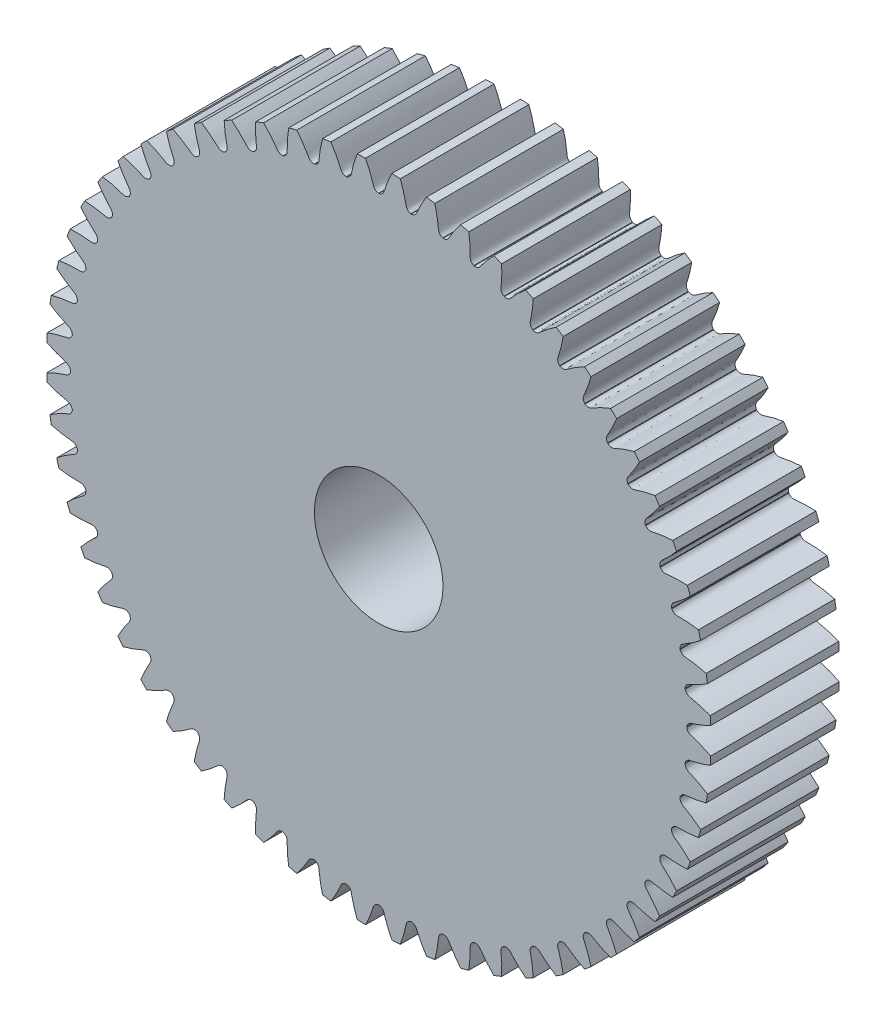
SolidWorks part; units mm, degrees
ref_plane "前视基准面" through (0, 0, 0) normal (0, 0, 1) x (1, 0, 0)
ref_plane "上视基准面" through (0, 0, 0) normal (0, 1, 0) x (1, 0, 0)
ref_plane "右视基准面" through (0, 0, 0) normal (1, 0, 0) x (0, 0, -1)
other "Configuration Table"
sketch "草图1" plane through (0, 0, 0) normal (0, 0, 1) x (1, 0, 0)
  circle A0 centre (0, 0) radius 15.5
extrude "凸台-拉伸1" add sketch "草图1" along normal blind 6
ref_axis "基准轴1" through (0, 0, -0.3) along (0, 0, 1)
sketch "草图2" plane through (0, 0, 0) normal (0, 0, 1) x (1, 0, 0)
  line L0 (0, 0) -> (0, 15.5) construction
  circle A0 centre (0, 0) radius 15.5 construction
  arc A1 (0.01, 14.375) -> (-0.01, 14.375) centre (0, 0) ccw
  arc A2 (2.1043, 17.5326) -> (-2.1043, 17.5326) centre (0, 0) ccw
  spline S0 degree 3 poles (0.01, 14.375) (0.2152, 14.4122) (0.2483, 14.5839) (0.3119, 14.7751) (0.342, 14.8616) (0.3759, 14.9526) (0.4137, 15.0482) (0.4555, 15.1483) (0.5016, 15.2526) (0.5522, 15.3611) (0.6074, 15.4736) (0.6675, 15.5901) (0.7325, 15.7102) (0.8027, 15.834) (0.8783, 15.9611) (0.9593, 16.0915) (1.046, 16.225) (1.1385, 16.3614) (1.237, 16.5005) (1.3416, 16.6422) (1.4525, 16.7862) (1.5697, 16.9323) (1.6935, 17.0805) (1.8698, 17.2831) (2.0086, 17.4331) (2.1043, 17.5326) knots 0 0 0 0 0.111713 0.134139 0.158036 0.183407 0.210249 0.238564 0.268351 0.299611 0.332343 0.366547 0.402223 0.439372 0.477993 0.518087 0.559653 0.602691 0.647201 0.693184 0.740639 0.789567 0.839967 0.891839 1 1 1 1
  spline S1 degree 3 poles (-0.01, 14.375) (-0.2152, 14.4122) (-0.2483, 14.5839) (-0.3119, 14.7751) (-0.342, 14.8616) (-0.3759, 14.9526) (-0.4137, 15.0482) (-0.4555, 15.1483) (-0.5016, 15.2526) (-0.5522, 15.3611) (-0.6074, 15.4736) (-0.6675, 15.5901) (-0.7325, 15.7102) (-0.8027, 15.834) (-0.8783, 15.9611) (-0.9593, 16.0915) (-1.046, 16.225) (-1.1385, 16.3614) (-1.237, 16.5005) (-1.3416, 16.6422) (-1.4525, 16.7862) (-1.5697, 16.9323) (-1.6935, 17.0805) (-1.8698, 17.2831) (-2.0086, 17.4331) (-2.1043, 17.5326) knots 0 0 0 0 0.111713 0.134139 0.158036 0.183407 0.210249 0.238564 0.268351 0.299611 0.332343 0.366547 0.402223 0.439372 0.477993 0.518087 0.559653 0.602691 0.647201 0.693184 0.740639 0.789567 0.839967 0.891839 1 1 1 1
extrude "切除-拉伸1" cut sketch "草图2" along normal through all
pattern_circular "阵列(圆周)1" count 60 every 6 about axis through (0, 0, -0.3) along (0, 0, 1) of "切除-拉伸1"
sketch "草图3" plane through (0, 0, 0) normal (0, 0, 1) x (1, 0, 0)
  circle A0 centre (0, 0) radius 15 construction
  dimension "Dn" = 30
sketch "草图4" plane through (0, 0, 6) normal (0, 0, 1) x (1, 0, 0)
  circle A0 centre (0, 0) radius 3
  dimension "D1" = 6
extrude "切除-拉伸2" cut sketch "草图4" against normal blind 10
